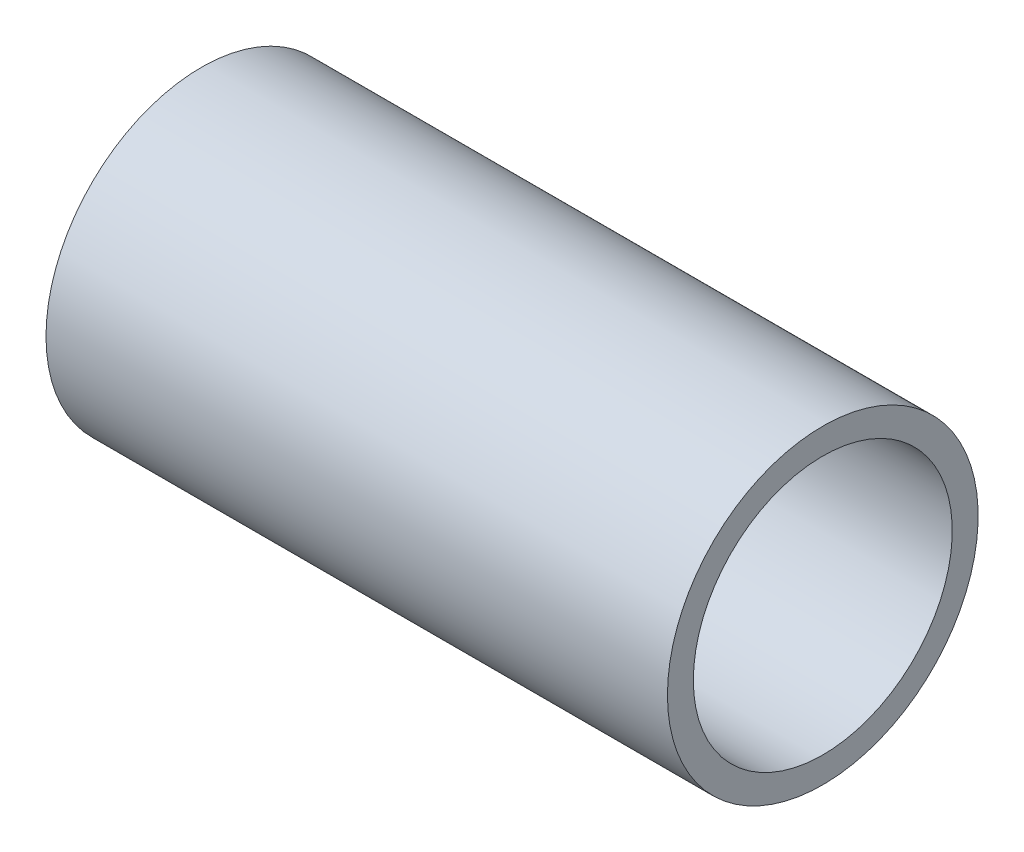
SolidWorks part; units mm, degrees
material "7075-O (SS)"
ref_plane "Front Plane" through (0, 0, 0) normal (0, 0, 1) x (1, 0, 0)
ref_plane "Top Plane" through (0, 0, 0) normal (0, 1, 0) x (1, 0, 0)
ref_plane "Right Plane" through (0, 0, 0) normal (1, 0, 0) x (0, 0, -1)
sketch "Sketch1" plane through (0, 0, 0) normal (1, 0, 0) x (0, 0, -1)
  circle A0 centre (0, 0) radius 1.5875
  circle A1 centre (0, 0) radius 1.905
  dimension "D1" = 3.175
  dimension "D2" = 0.3175
extrude "Boss-Extrude1" add sketch "Sketch1" along normal blind 7.62
ref_axis "Axis1" through (7.62, 0, 0) along (-1, 0, 0)
